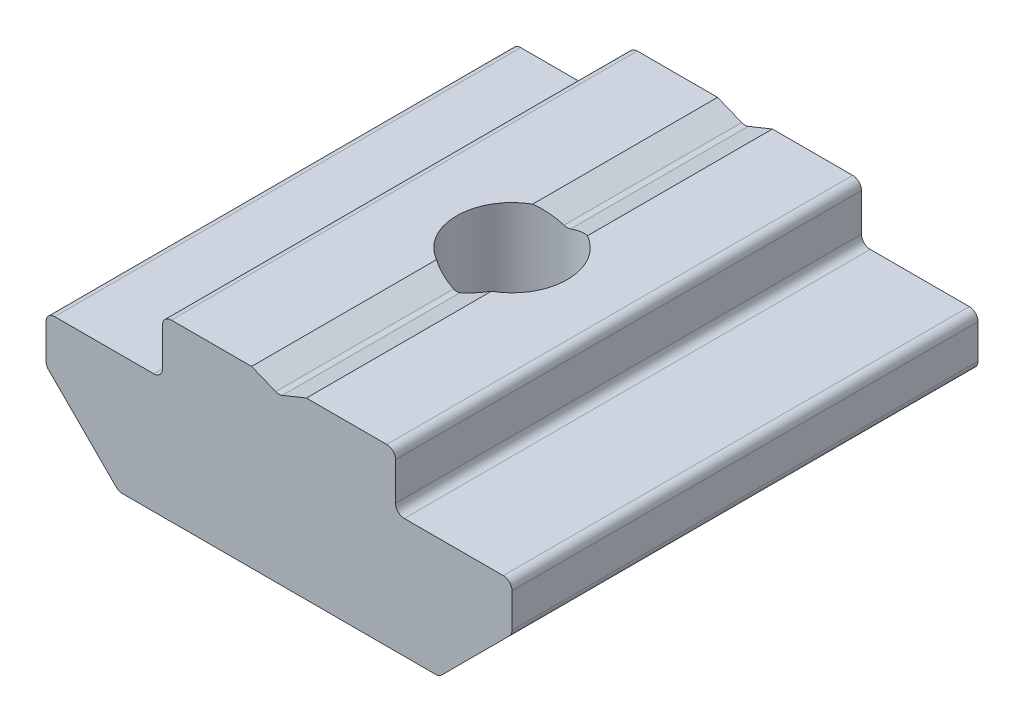
SolidWorks part; units mm, degrees
ref_plane "Front Plane" through (0, 0, 0) normal (0, 0, 1) x (1, 0, 0)
ref_plane "Top Plane" through (0, 0, 0) normal (0, 1, 0) x (1, 0, 0)
ref_plane "Right Plane" through (0, 0, 0) normal (1, 0, 0) x (0, 0, -1)
sketch "Sketch1" plane through (0, 0, 0) normal (0, 0, 1) x (1, 0, 0)
  line L0 (-8, 4.1) -> (8, 4.1) construction
  line L1 (0, 0) -> (0, 6) construction
  line L2 (-4, 6) -> (4, 6) construction
  line L3 (-2, 0) -> (2, 0) construction
  line L4 (2.0758, 0.0437) -> (1.4696, -0.3063) construction
  line L5 (1.4696, -0.3063) -> (2.0758, -0.6563) construction
  line L6 (2.0758, -0.6563) -> (2.0758, 0.0437) construction
  line L7 (1.5453, -0.2625) -> (1.5453, -0.35) construction
  line L8 (2, 0) -> (2, -0.6125) construction
  line L9 (2.0379, 0.0219) -> (2.0379, -0.6344) construction
  line L10 (2.0758, -0.3063) -> (2, -0.3063) construction
  line L11 (1.5453, -0.3063) -> (1.4696, -0.3063) construction
  line L13 (-0.9405, 6) -> (0, 5.62) construction
  line L14 (0, 5.62) -> (0.9405, 6) construction
  point P6 (0, 4.1)
  point P21 (2.0379, -0.3063)
  point P23 (0, 2.5)
  point P24 (8, 4.1)
  dimension "Thickness" = 6
  dimension "Width" = 16
  dimension "Head Length" = 8
  dimension "Thread Size" = 4
  dimension "Thread Pitch" = 0.7
  dimension "D2" = 0.0875
  dimension "Head Height" = 1.9
  dimension "Undercut Height" = 2.5
  dimension "Cut Angle" = 136
  dimension "D1" = 0.38
sketch "Sketch2" plane through (0, 0, 0) normal (0, 1, 0) x (0, 0, -1)
  line L0 (-8, 0) -> (8, 0) construction
  line L1 (8, 8) -> (8, -8) construction
  line L2 (0, 8) -> (0, -8) construction
  line L3 (8, 8) -> (-8, 8) construction
  line L4 (-8, 8) -> (-8, 0) construction
  dimension "Length" = 16
sketch "Sketch4" plane through (0, 0, 0) normal (0, 0, 1) x (1, 0, 0)
  line L0 (-8, 4.1) -> (-8, 2.5)
  line L1 (-8, 2.5) -> (-5.5, 0)
  line L2 (-5.5, 0) -> (5.5, 0)
  line L3 (0, 0) -> (0, 6) construction
  line L4 (0, 0) -> (0, 4.1) construction
  line L7 (-8, 4.1) -> (8, 4.1) construction
  line L8 (8, 4.1) -> (4, 4.1)
  line L11 (8, 2.5) -> (5.5, 0)
  line L12 (8, 4.1) -> (8, 2.5)
  line L13 (0, 4.1) -> (0, 6) construction
  line L14 (-4, 4.1) -> (-4, 6)
  line L15 (-4, 6) -> (-0.9405, 6)
  line L16 (4, 6) -> (4, 4.1)
  line L17 (-4, 4.1) -> (-8, 4.1)
  line L18 (0, 5.62) -> (-0.9405, 6)
  line L21 (0.9405, 6) -> (0, 5.62)
  line L22 (0.9405, 6) -> (4, 6)
  dimension "D1" = 135
extrude "Boss-Extrude1" add sketch "Sketch4" along normal up to vertex (8 mm away) and the other way up to vertex (8 mm away) up to point (0, 0, 8) other way up to point (0, 0, -8)
sketch "Sketch17" plane through (2.25, 0, 0) normal (0, 1, 0) x (1, 0, 0)
  line L0 (-3.6642, -1.4142) -> (-2.25, 0) construction
  line L1 (-2.25, 0) -> (-2.25, -2) construction
  circle A0 centre (-2.25, 0) radius 2 construction
  dimension "D1" = 45
sketch "Sketch9" plane through (0, 0, 0) normal (0, 1, 0) x (1, 0, 0)
  circle A0 centre (0, 0) radius 1.9
  point P3 (-1.9, 0)
  dimension "D1" = 0.1
extrude "Cut-Extrude2" cut sketch "Sketch9" along normal through all
fillet "Fillet1" radius 0.3 12 edges at (-4, 6, 0) (-4, 4.1, 0) (-8, 4.1, 0) (-8, 2.5, 0) (-5.5, 0, 0) (5.5, 0, 0) (8, 2.5, 0) (8, 4.1, 0) (4, 4.1, 0) (4, 6, 0) (0, 5.62, -4.95) (0, 5.62, 4.95)
sketch "Sketch10" [suppressed] plane through (0, 0, 0) normal (0, 1, 0) x (1, 0, 0)
  circle A0 centre (0, 0) radius 2
ref_axis "Center Axis 1" through (0, 6.8549, 0) along (0, -1, 0)
ref_plane "Contact Plane 1" through (0, 4.1, 0) normal (0, 1, 0) x (1, 0, 0)
curve "Helix/Spiral1" [suppressed] pitch 0.7 height 6.7 turns 9.5714
sketch "Sketch12" [suppressed] plane through (0, 0, 0) normal (0, 0, 1) x (1, 0, 0)
  line L0 (2.0379, 0.0219) -> (2.0379, -0.6344)
  line L1 (2.0379, -0.6344) -> (1.5453, -0.35)
  line L2 (1.5453, -0.35) -> (1.5453, -0.2625)
  line L3 (1.5453, -0.2625) -> (2.0379, 0.0219)
sweep "Sweep1" [suppressed] add profiles "Sketch12" path "Helix/Spiral1"
sketch "Sketch13" [suppressed] plane through (0, 0, 0) normal (0, -1, 0) x (1, 0, 0)
  circle A0 centre (0, 0) radius 8
extrude "Cut-Extrude3" [suppressed] cut sketch "Sketch13" along normal through all
sketch "Sketch14" [suppressed] plane through (0, 6, 0) normal (0, 1, 0) x (1, 0, 0)
  circle A0 centre (0, 0) radius 8
extrude "Cut-Extrude4" [suppressed] cut sketch "Sketch14" along normal through all
sketch "Sketch15" [suppressed] plane through (0, 0, 0) normal (0, -1, 0) x (1, 0, 0)
  circle A1 centre (0, 0) radius 2
  circle A2 centre (0, 0) radius 2
  dimension "D1" = 0
extrude "Cut-Extrude5" [suppressed] cut sketch "Sketch15" against normal through all draft 45
sketch "Sketch16" [suppressed] plane through (0, 6, 0) normal (0, 1, 0) x (1, 0, 0)
  circle A1 centre (0, 0) radius 2
  circle A2 centre (0, 0) radius 2
  dimension "D1" = 0
extrude "Cut-Extrude6" [suppressed] cut sketch "Sketch16" against normal through all draft 45
sketch "Sketch18" [suppressed] plane through (0, 0, 0) normal (0, 0, 1) x (1, 0, 0)
  line L0 (-0.9405, 6) -> (-0.1124, 5.6654)
  line L1 (-4, 6) -> (4, 6) construction
  line L2 (0, 0) -> (0, 6) construction
  line L3 (0.1124, 5.6654) -> (0.9405, 6)
  line L4 (-0.9405, 6) -> (0.9405, 6)
  line L5 (-4, 5.7) -> (-4, 6)
  line L6 (-4, 6) -> (-3.7, 6)
  line L7 (4, 5.7) -> (4, 6)
  line L8 (4, 6) -> (3.7, 6)
  line L9 (-0.9405, 6) -> (-3.7, 6) construction
  arc A0 (0.1124, 5.6654) -> (-0.1124, 5.6654) centre (0, 5.9436) cw
  arc A1 (-3.7, 6) -> (-4, 5.7) centre (-3.7, 5.7) ccw
  arc A2 (3.7, 6) -> (4, 5.7) centre (3.7, 5.7) cw
  point P12 (0, 5.62)
  dimension "D1" = 0.3
extrude "Cut-Extrude7" [suppressed] cut sketch "Sketch18" against normal through all both and the other way through all
sketch "Sketch20" [suppressed] plane through (0, 0, 8) normal (0, 0, 1) x (1, 0, 0)
  line L1 (-4, 5.7) -> (-4.3, 5.7)
  line L2 (-4, 5.7) -> (-4, 4.4)
  line L3 (-4, 4.4) -> (-4.3, 4.4)
  line L4 (-4.3, 5.7) -> (-4.3, 4.4)
extrude "Boss-Extrude2" [suppressed] add sketch "Sketch20" against normal up to vertex from offset 2 offset against normal yes
sketch "Sketch19" [suppressed] plane through (0, 0, 8) normal (0, 0, 1) x (1, 0, 0)
  line L0 (-7.7, 4.1) -> (-7.7, 7.9)
  line L1 (-7.7, 7.9) -> (7.7, 7.9)
  line L2 (7.7, 7.9) -> (7.7, 4.1)
  line L3 (-3.7, 6) -> (-7.7, 6) construction
  line L13 (4, 4.4) -> (4, 5.7)
  line L14 (-0.9405, 6) -> (-3.7, 6)
  line L15 (0.9405, 6) -> (0.1124, 5.6654)
  line L16 (-0.1124, 5.6654) -> (-0.9405, 6)
  line L17 (3.7, 6) -> (0.9405, 6)
  line L18 (-4, 5.7) -> (-4, 4.4)
  line L19 (-4.3, 4.1) -> (-7.7, 4.1)
  line L20 (-8, 3.8) -> (-8, 2.6243)
  line L21 (-7.9121, 2.4121) -> (-5.5879, 0.0879)
  line L22 (-5.3757, 0) -> (5.3757, 0)
  line L23 (5.5879, 0.0879) -> (7.9121, 2.4121)
  line L24 (8, 2.6243) -> (8, 3.8)
  line L25 (7.7, 4.1) -> (4.3, 4.1)
  line L26 (4, 4.4) -> (4, 5.7)
  line L27 (-0.9405, 6) -> (-3.7, 6)
  line L28 (0.9405, 6) -> (0.1124, 5.6654)
  line L29 (-0.1124, 5.6654) -> (-0.9405, 6)
  line L32 (-4.3, 4.1) -> (-7.7, 4.1)
  line L38 (7.7, 4.1) -> (4.3, 4.1)
  line L43 (-4, 5.7) -> (-4, 4.4)
  line L44 (3.7, 6) -> (0.9405, 6)
  arc A11 (4, 5.7) -> (3.7, 6) centre (3.7, 5.7) ccw
  arc A12 (-0.1124, 5.6654) -> (0.1124, 5.6654) centre (0, 5.9436) ccw
  arc A13 (-3.7, 6) -> (-4, 5.7) centre (-3.7, 5.7) ccw
  arc A14 (-4.3, 4.1) -> (-4, 4.4) centre (-4.3, 4.4) ccw
  arc A15 (-7.7, 4.1) -> (-8, 3.8) centre (-7.7, 3.8) ccw
  arc A16 (-8, 2.6243) -> (-7.9121, 2.4121) centre (-7.7, 2.6243) ccw
  arc A17 (-5.5879, 0.0879) -> (-5.3757, 0) centre (-5.3757, 0.3) ccw
  arc A18 (5.3757, 0) -> (5.5879, 0.0879) centre (5.3757, 0.3) ccw
  arc A19 (7.9121, 2.4121) -> (8, 2.6243) centre (7.7, 2.6243) ccw
  arc A20 (8, 3.8) -> (7.7, 4.1) centre (7.7, 3.8) ccw
  arc A21 (4, 4.4) -> (4.3, 4.1) centre (4.3, 4.4) ccw
  arc A22 (4, 5.7) -> (3.7, 6) centre (3.7, 5.7) ccw
  arc A23 (-0.1124, 5.6654) -> (0.1124, 5.6654) centre (0, 5.9436) ccw
  arc A24 (-3.7, 6) -> (-4, 5.7) centre (-3.7, 5.7) ccw
  arc A25 (-4.3, 4.1) -> (-4, 4.4) centre (-4.3, 4.4) ccw
  arc A32 (4, 4.4) -> (4.3, 4.1) centre (4.3, 4.4) ccw
  dimension "D1" = 0
extrude "Cut-Extrude8" [suppressed] cut sketch "Sketch19" against normal up to vertex
equation "\"D2@Sketch1\" = \"Thread Pitch@Sketch1\" / 8"
equation "\"D3@Helix/Spiral1\" = \"Thickness@Sketch1\" + \"Thread Pitch@Sketch1\""
equation "\"D4@Helix/Spiral1\"=\"Thread Pitch@Sketch1\""
equation "\"D1@Sketch1\"=\"Head Height@Sketch1\"/5"
equation "\"D1@Sketch18\"=\"D1@Fillet1\""
